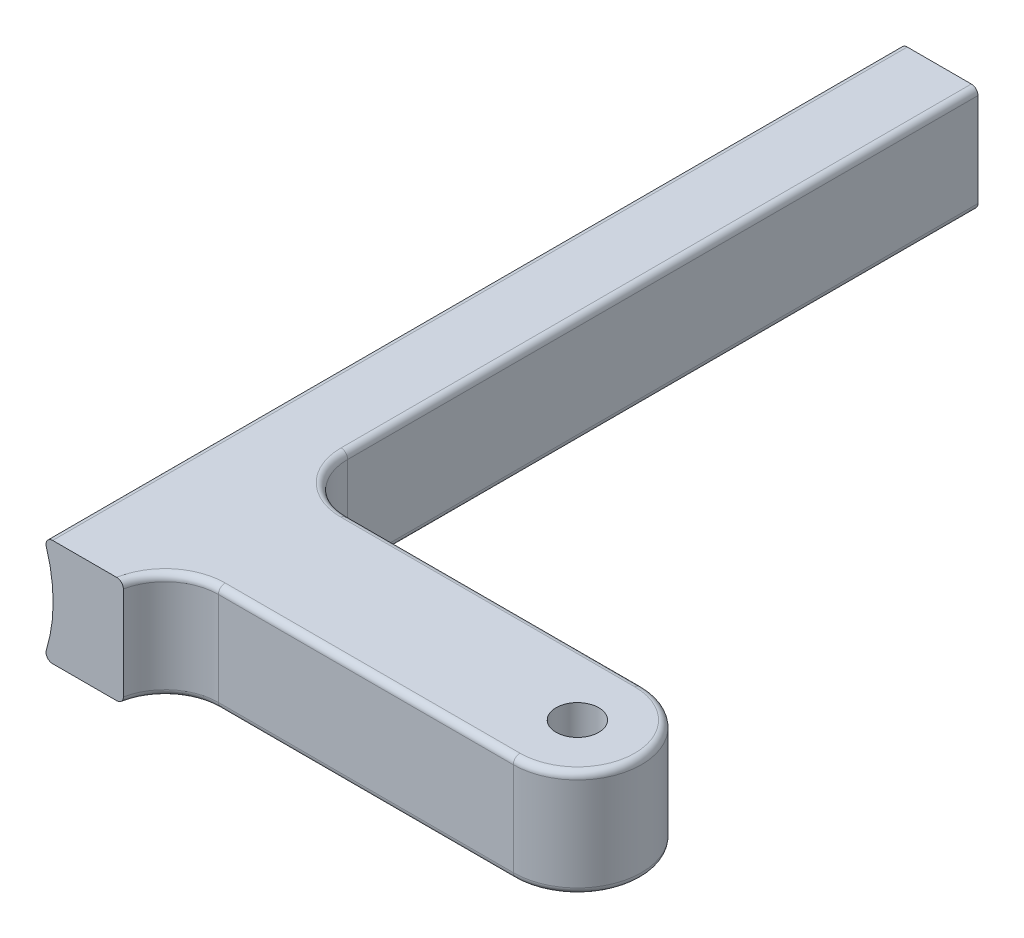
SolidWorks part; units mm, degrees
ref_plane "Front Plane" through (0, 0, 0) normal (0, 0, 1) x (1, 0, 0)
ref_plane "Top Plane" through (0, 0, 0) normal (0, 1, 0) x (1, 0, 0)
ref_plane "Right Plane" through (0, 0, 0) normal (1, 0, 0) x (0, 0, -1)
sketch "Sketch1" plane through (0, 0, 0) normal (0, 1, 0) x (1, 0, 0)
  line L8 (-20.6375, -3.81) -> (-20.6375, -6.35)
  line L10 (-20.6375, -6.35) -> (-25.4, -6.35)
  line L11 (-25.4, -6.35) -> (-25.4, 44.45)
  line L12 (-25.4, 44.45) -> (-20.6375, 44.45)
  line L13 (-20.6375, 44.45) -> (-20.6375, 3.81)
  line L14 (-20.6375, -3.81) -> (0, -3.81)
  line L15 (-20.6375, 3.81) -> (0, 3.81)
  circle A0 centre (0, 0) radius 1.27
  arc A1 (0, -3.81) -> (0, 3.81) centre (0, 0) ccw
  dimension "D1" = 2.54
  dimension "D2" = 2.54
  dimension "D3" = 4.7625
  dimension "D4" = 25.4
  dimension "D5" = 6.35
  dimension "D6" = 50.8
extrude "Boss-Extrude1" add sketch "Sketch1" along normal mid plane 6.35
fillet "Fillet1" radius 3.175 2 edges at (-20.6375, 0, 3.81) (-20.6375, 0, -3.81)
sketch "Sketch3" plane through (0, 0, 6.35) normal (0, 0, 1) x (1, 0, 0)
  arc A0 (-25.4, 3.175) -> (-25.4, -3.175) centre (-33.7037, 0) cw construction
  circle A1 centre (-33.7037, 0) radius 8.89
  dimension "D1" = 17.78
extrude "Cut-Extrude1" cut sketch "Sketch3" against normal through all both and the other way through all
fillet "Fillet2" radius 0.3969 14 edges at (-25.4, 3.175, -19.05) (-25.4, -3.175, -19.05) (-19.5347, -3.175, 4.5257) (-20.6375, -3.175, -25.7175) (-19.7076, -3.175, -4.7399) (-8.7312, -3.175, -3.81) (3.81, -3.175, 0) (-20.6375, 3.175, -25.7175) (-19.7076, 3.175, -4.7399) (-8.7312, 3.175, -3.81) (3.81, 3.175, 0) (-8.7633, 3.175, 3.81) (-8.7633, -3.175, 3.81) (-19.5347, 3.175, 4.5257)
